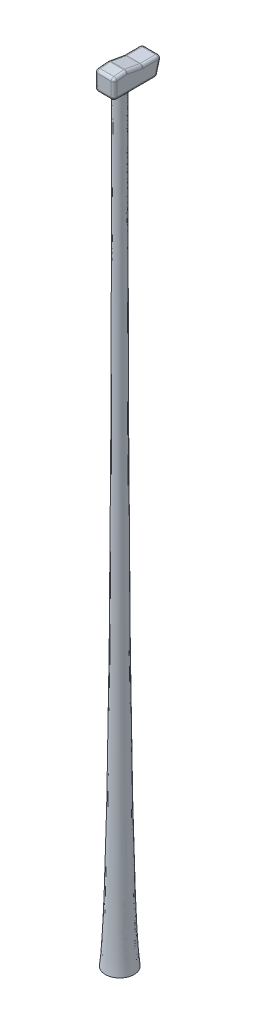
SolidWorks part; units mm, degrees
ref_plane "Ebene vorne" through (0, 0, 0) normal (0, 0, 1) x (1, 0, 0)
ref_plane "Ebene oben" through (0, 0, 0) normal (0, 1, 0) x (1, 0, 0)
ref_plane "Ebene rechts" through (0, 0, 0) normal (1, 0, 0) x (0, 0, -1)
sketch "Skizze2" plane through (0, 0, 0) normal (1, 0, 0) x (0, 0, -1)
  line L0 (500, -1000) -> (500, 1000)
  line L1 (-500, -500) -> (500, -500) construction
  line L2 (-500, -500) -> (-500, 500) construction
  line L3 (-500, 500) -> (500, 500) construction
  line L4 (500, -500) -> (500, 500) construction
  line L5 (-500, -500) -> (500, 500) construction
  line L6 (-500, 500) -> (500, -500) construction
  line L7 (500, 1000) -> (1850, 1118.1097)
  line L8 (1850, 1118.1097) -> (3500, 827.1702)
  line L9 (3500, 827.1702) -> (5500, 827.1702)
  line L10 (5500, 827.1702) -> (5010.4112, -1000)
  line L11 (5010.4112, -1000) -> (500, -1000)
  point P0 (0, 0)
  dimension "D1" = 1000
  dimension "D2" = 1000
  dimension "D3" = 95
  dimension "D4" = 165
  dimension "D5" = 75
  dimension "D6" = 1350
  dimension "D7" = 1650
  dimension "D8" = 5000
  dimension "D9" = 500
  dimension "D10" = 500
extrude "Aufsatz-Linear austragen1" add sketch "Skizze2" along normal blind 1000 and the other way blind 1000
fillet "Verrundung1" radius 300 18 edges at (0, -1000, -5010.4112) (-1000, -86.4149, -5255.2056) (-1000, -1000, -2755.2056) (-1000, 0, -500) (0, -1000, -500) (1000, 0, -500) (1000, -86.4149, -5255.2056) (1000, -1000, -2755.2056) (-1000, 827.1702, -4500) (0, 827.1702, -5500) (1000, 827.1702, -4500) (-1000, 972.6399, -2675) (0, 827.1702, -3500) (1000, 972.6399, -2675) (-1000, 1059.0548, -1175) (0, 1118.1097, -1850) (1000, 1059.0548, -1175) (0, 1000, -500)
sketch "Skizze3" plane through (0, 0, 0) normal (1, 0, 0) x (0, 0, -1)
  line L0 (2100, 0) -> (2100, -215.2925) construction
  line L1 (2100, -700) -> (1400, -700)
  line L2 (800, -700) -> (4780.2131, -700) construction
  line L3 (1400, -700) -> (1400, -1200)
  line L4 (1400, -1200) -> (1450, -1200)
  line L5 (1450, -1200) -> (1450, -1000)
  line L6 (4780.2131, -1000) -> (800, -1000) construction
  line L7 (1450, -1000) -> (1480, -1000)
  line L8 (1480, -1000) -> (1480, -1200)
  line L9 (2100, -700) -> (2100, -80000)
  line L10 (600, -80000) -> (2100, -80000)
  line L11 (-37.4147, 0) -> (55.262, 0) construction
  line L13 (500, -700) -> (500, 725.1006) construction
  line L14 (1400, -1200) -> (161.2362, -1200) construction
  spline S0 degree 3 poles (1480, -1200) (1480, -1555.3967) (1606.3425, -71467.2124) (600, -80000) knots 0 0 0 0 1 1 1 1
  dimension "D1" = 500
  dimension "D2" = 1600
  dimension "D3" = 700
  dimension "D4" = 50
  dimension "D5" = 30
  dimension "D6" = 750
  dimension "D7" = 80000
  dimension "D8" = 48000
  dimension "D9" = 1500
revolve "Rotation1" add sketch "Skizze3" angle 360 about L0
